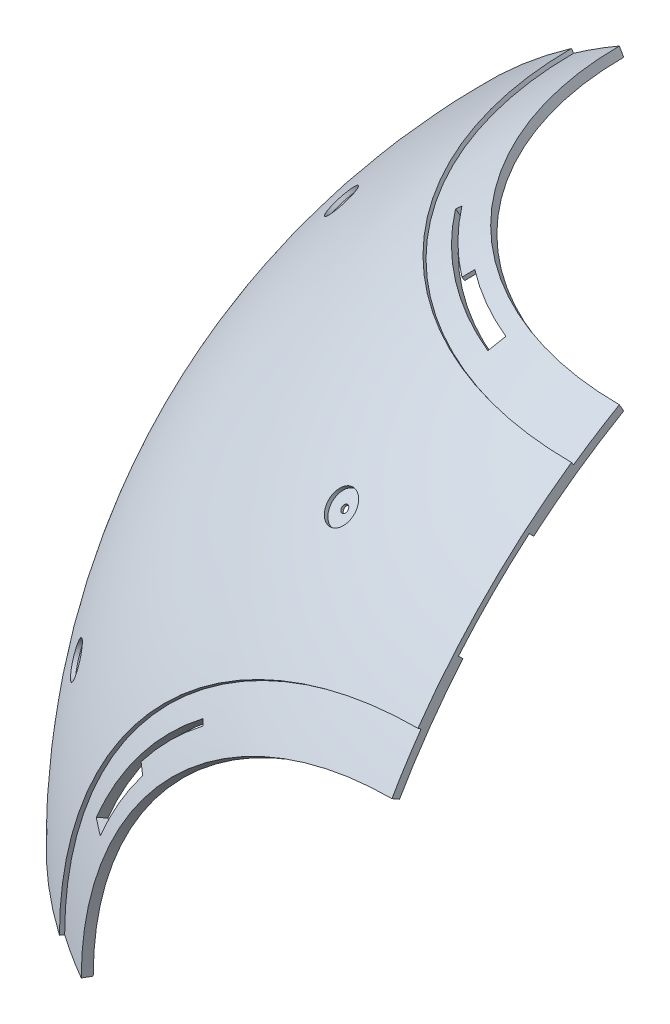
SolidWorks part; units mm, degrees
ref_plane "Front Plane" through (0, 0, 0) normal (0, 0, 1) x (1, 0, 0)
ref_plane "Top Plane" through (0, 0, 0) normal (0, 1, 0) x (1, 0, 0)
ref_plane "Right Plane" through (0, 0, 0) normal (1, 0, 0) x (0, 0, -1)
sketch "Sketch1" plane through (0, 0, 0) normal (0, 0, 1) x (1, 0, 0)
  line L0 (0, 0) -> (0, 282.4311)
  line L1 (-122.5, 212.1762) -> (-124.25, 215.2073)
  line L2 (-142.5337, 203.5593) -> (-143.3941, 204.788)
  line L3 (-245, 0) -> (-250, 0)
  arc A0 (-143.3941, 204.788) -> (-250, 0) centre (0, 0) ccw
  arc A1 (-124.25, 215.2073) -> (-142.5337, 203.5593) centre (0, 0) ccw
  arc A2 (-122.5, 212.1762) -> (-245, 0) centre (0, 0) ccw
  dimension "D1" = 500
  dimension "D2" = 497
  dimension "D3" = 490
  dimension "D4" = 5
  dimension "D5" = 30
revolve "Revolve1" add sketch "Sketch1" angle 90 about L0 region at (-214.3425, 123.7507, 0)
sketch "Sketch2" plane through (0, 0, 0) normal (1, 0, 0) x (0, 0, -1)
  line L0 (0, 0) -> (-288.7114, 0)
  line L1 (-212.1762, 122.5) -> (-215.2073, 124.25)
  line L2 (-203.5593, 142.5337) -> (-204.788, 143.3941)
  arc A0 (-204.788, 143.3941) -> (-250, 0) centre (0, 0) ccw
  arc A1 (-212.1762, 122.5) -> (-245, 0) centre (0, 0) ccw
  arc A2 (-203.5593, 142.5337) -> (-215.2073, 124.25) centre (0, 0) ccw
  dimension "D1" = 497
  dimension "D2" = 490
  dimension "D3" = 5
  dimension "D4" = 30
revolve "Cut-Revolve2" cut sketch "Sketch2" angle 360 about L0 region at (0, 1.5073, 247.5)
sketch "Sketch3" plane through (0, 0, 0) normal (0, 0, -1) x (-1, 0, 0)
  line L0 (0, 0) -> (307.3195, 0)
  line L1 (203.5593, 142.5337) -> (204.788, 143.3941)
  line L2 (0, 0) -> (215.2073, 124.25)
  arc A0 (245, 0) -> (212.1762, 122.5) centre (0, 0) ccw
  arc A1 (250, 0) -> (204.788, 143.3941) centre (0, 0) ccw
  arc A2 (215.2073, 124.25) -> (203.5593, 142.5337) centre (0, 0) ccw
  dimension "D1" = 497
  dimension "D2" = 30
  dimension "D3" = 5
revolve "Cut-Revolve3" cut sketch "Sketch3" angle 360 about L0 region at (-238.1077, 63.8008, 0)
sketch "Sketch10" plane through (0, 0, 0) normal (0, 0, 1) x (1, 0, 0)
  line L0 (0, 0) -> (-235.3166, 0)
  line L1 (0, 0) -> (-214.7234, 214.7234)
  dimension "D1" = 45
ref_plane "Plane1" through (0, 0, 0) normal (0, -0.3827, 0.9239) x (-1, 0, 0)
sketch "Sketch11" plane through (0, 0, 0) normal (0, -0.3827, 0.9239) x (-1, 0, 0)
  line L0 (0, 0) -> (211.8811, -129.8409)
  line L1 (0, 0) -> (208.4096, -135.3428)
  line L2 (0, 0) -> (204.788, -143.3941)
  line L3 (0, 0) -> (271.2872, 0)
  circle A0 centre (0, 0) radius 248.5
  circle A1 centre (0, 0) radius 245
  dimension "D1" = 497
  dimension "D2" = 490
  dimension "D3" = 1.5
  dimension "D4" = 2
revolve "Cut-Revolve4" cut sketch "Sketch11" angle 15 about L0 region at (-208.6809, 121.6452, 50.3871) reverse direction yes
sketch "Sketch12" plane through (0, 0, 0) normal (0, 0.6088, -0.7934) x (1, 0, 0)
  line L0 (0, 0) -> (-209.5828, -133.519)
  line L1 (0, 0) -> (-208.4096, -135.3428)
  line L2 (0, 0) -> (-204.788, -143.3941)
  line L3 (0, 0) -> (-211.8811, -129.8409)
  circle A0 centre (0, 0) radius 248.5
  circle A1 centre (0, 0) radius 245
  circle A2 centre (0, 0) radius 247
  dimension "D1" = 490
  dimension "D4" = 494
  dimension "D2" = 2
  dimension "D3" = 0.5
revolve "Cut-Revolve5" cut sketch "Sketch12" angle 15 about L0 region at (-206.8961, 105.5795, 81.014) region at (-208.6183, 103.4209, 79.3577) region at (-208.3674, 106.3303, 81.5901) reverse direction yes
ref_plane "Plane2" through (0, 0, 0) normal (0, -0.7071, 0.7071) x (-1, 0, 0)
sketch "Sketch15" plane through (0, 0, 0) normal (0, 1, 0) x (1, 0, 0)
  line L1 (0, 0) -> (-189.3752, -189.3752)
  line L2 (0, 0) -> (0, -178.2847)
  dimension "D1" = 45
ref_plane "Plane3" through (0, 0, 0) normal (-0.7071, 0, -0.7071) x (-0.7071, 0, 0.7071)
ref_axis "Axis1" through (9.4688, -9.4688, -9.4688) along (-0.5774, 0.5774, 0.5774)
pattern_circular "CirPattern5" count 3 every 120 about axis through (9.4688, -9.4688, -9.4688) along (-0.5774, 0.5774, 0.5774) of "Cut-Revolve4", "Cut-Revolve5"
sketch "Sketch18" plane through (0, 0, 0) normal (-0.7071, 0, -0.7071) x (-0.7071, 0, 0.7071)
  line L0 (0, 0) -> (0, 83.9389)
ref_plane "Plane5" through (0, 0, 0) normal (-0.7071, 0, 0.7071) x (0, 1, 0)
sketch "Sketch19" plane through (0, 0, 0) normal (-0.7071, 0, 0.7071) x (0, 1, 0)
  line L0 (0, 64.3165) -> (0, -64.3165)
sketch "Sketch20" plane through (0, 0, 0) normal (0, -1, 0) x (1, 0, 0)
  line L0 (0, 0) -> (-202.4375, 202.4375)
  line L1 (14.1421, 14.1421) -> (-188.2954, 216.5796)
  line L2 (-14.1421, -14.1421) -> (-216.5796, 188.2954)
  circle A0 centre (0, 0) radius 247.5
  circle A1 centre (0, 0) radius 245
  dimension "D3" = 495
  dimension "D1" = 20
  dimension "D2" = 20
revolve "Cut-Revolve6" cut sketch "Sketch20" angle 20 about L0 region at (-181.0082, 0, 166.8583) region at (-166.8583, 0, 181.0082) reverse direction yes
pattern_circular "CirPattern6" count 3 over 360 about axis through (9.4688, -9.4688, -9.4688) along (-0.5774, 0.5774, 0.5774) of "Cut-Revolve6"
ref_plane "Plane6" through (0, 0, 0) normal (0.183, 0.9659, -0.183) x (0.7071, 0, 0.7071)
sketch "Sketch21" plane through (0, 0, 0) normal (0.183, 0.9659, -0.183) x (0.7071, 0, 0.7071)
  line L0 (0, 0) -> (0, -320.9384)
sketch "Sketch22" plane through (0, 0, 0) normal (-0.7071, 0, -0.7071) x (-0.7071, 0, 0.7071)
  line L0 (0, 0) -> (310.0027, 83.065) construction
  line L1 (0, 0) -> (310.0027, 83.065)
  line L2 (0.3882, -1.4489) -> (310.391, 81.6161)
  line L3 (1.6823, -6.2785) -> (311.6851, 76.7865)
  circle A0 centre (0, 0) radius 250
  circle A1 centre (0, 0) radius 248.5
  circle A2 centre (0, 0) radius 299.5165
  circle A3 centre (0, 0) radius 234.5409
  dimension "D1" = 497
  dimension "D2" = 500
  dimension "D3" = 1.5
  dimension "D4" = 5
revolve "Cut-Revolve13" cut sketch "Sketch22" angle 360 about L1 region at (-165.0977, 61.7852, 165.0977) region at (-170.3771, 63.7858, 170.3771) region at (-170.9482, 60.6374, 170.9482)
pattern_circular "CirPattern8" count 3 every 120 about axis through (9.4688, -9.4688, -9.4688) along (-0.5774, 0.5774, 0.5774) of "Cut-Revolve13"
